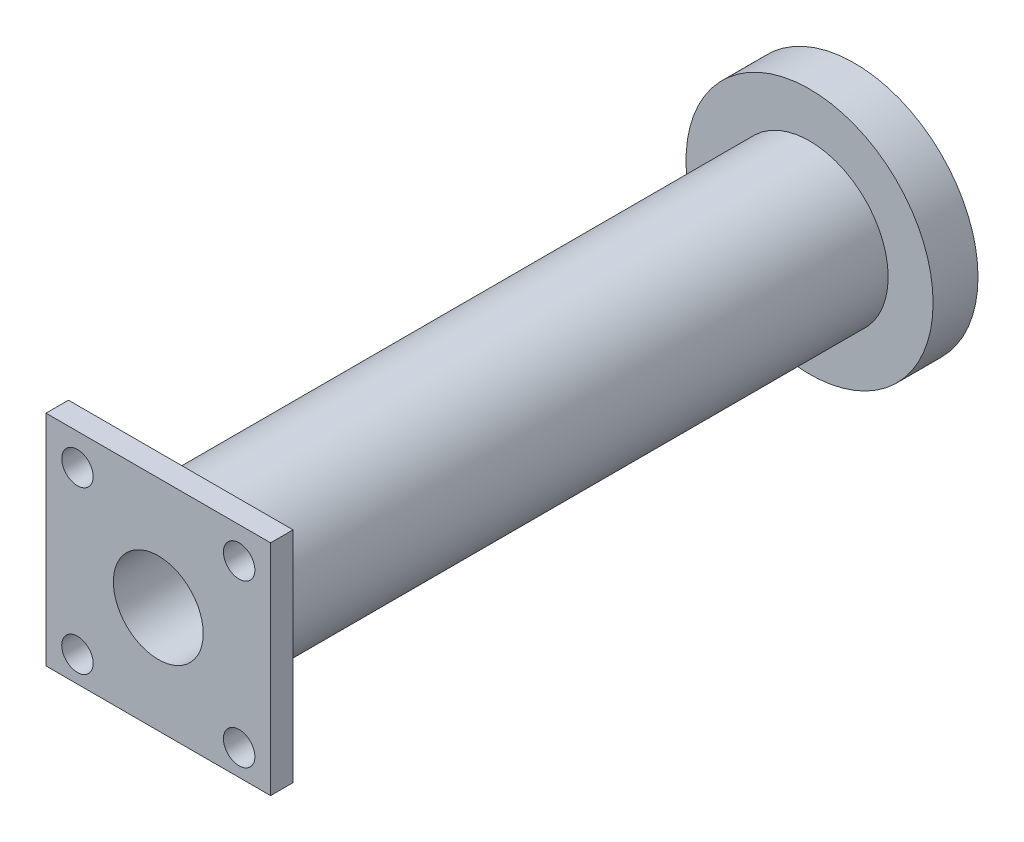
SolidWorks part; units mm, degrees
material "Plain Carbon Steel"
ref_plane "Front Plane" through (0, 0, 0) normal (0, 0, 1) x (1, 0, 0)
ref_plane "Top Plane" through (0, 0, 0) normal (0, 1, 0) x (1, 0, 0)
ref_plane "Right Plane" through (0, 0, 0) normal (1, 0, 0) x (0, 0, -1)
sketch "Sketch1" plane through (0, 0, 0) normal (0, 0, 1) x (1, 0, 0)
  circle A0 centre (0, 0) radius 88.9
  circle A1 centre (0, 0) radius 50.8
  circle A2 centre (0, 0) radius 139.7
  dimension "D1" = 177.8
  dimension "D2" = 101.6
  dimension "D3" = 279.4
extrude "Boss-Extrude3" add sketch "Sketch1" along normal blind 50.8 contours A2 A0 region at (-135.7487, 0, 0)
extrude "Boss-Extrude4" add sketch "Sketch1<4>" along normal blind 762 contours A0 A1 region at (-86.3855, 0, 0)
sketch "Sketch1<4>" plane through (0, 0, 0) normal (0, 0, 1) x (1, 0, 0) same geometry as "Sketch1"
sketch "Sketch3" plane through (0, 0, 762) normal (0, 0, 1) x (1, 0, 0)
  line L0 (0, -1254) -> (0, -127) construction
  line L1 (-127, 127) -> (127, 127)
  line L2 (-127, 127) -> (-127, -120.65)
  line L4 (127, 127) -> (127, -120.65)
  line L5 (-127, 127) -> (120.65, -120.65) construction
  line L6 (-120.65, -120.65) -> (127, 127) construction
  line L7 (0, 0) -> (50000, 0) construction
  line L8 (-127, -120.65) -> (127, -120.65)
  line L9 (0, -120.65) -> (0, 50000) construction
  circle A0 centre (-91.44, 91.44) radius 17.78
  circle A1 centre (91.44, 91.44) radius 17.78
  circle A2 centre (91.44, -91.44) radius 17.78
  circle A3 centre (-91.44, -91.44) radius 17.78
  circle A4 centre (0, 0) radius 50.8 construction
  circle A5 centre (0, 0) radius 50.8
  point P0 (0, 0)
  dimension "D3" = 35.56
  dimension "D1" = 254
  dimension "D2" = 247.65
  dimension "D4" = 35.56
  dimension "D5" = 35.56
extrude "Boss-Extrude5" add sketch "Sketch3" along normal blind 25.4
equation "\"b\"=1"
